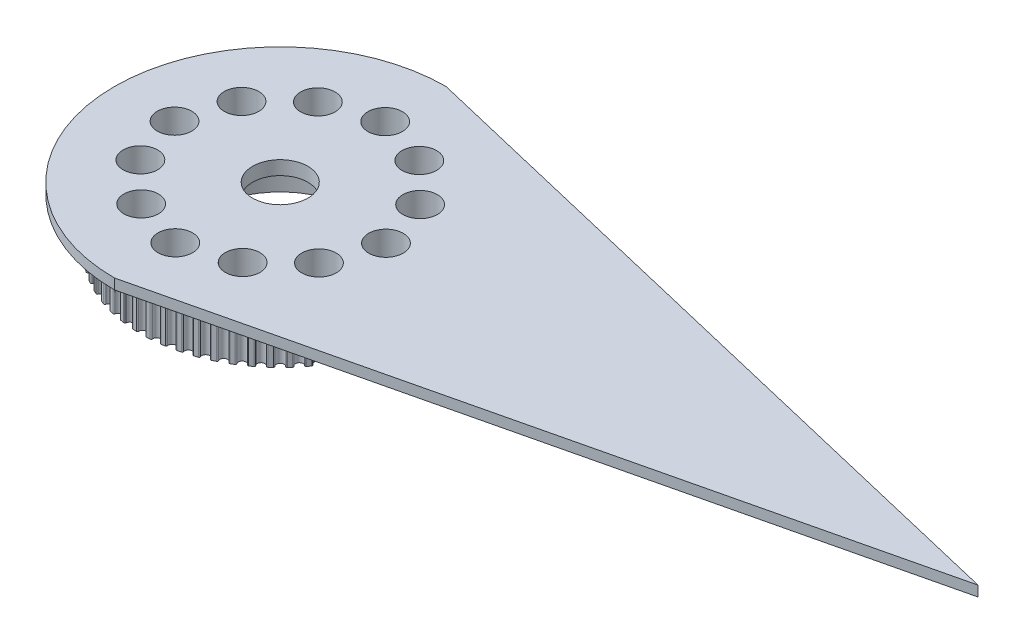
SolidWorks part; units mm, degrees
ref_plane "Front Plane" through (0, 0, 0) normal (0, 0, 1) x (1, 0, 0)
ref_plane "Top Plane" through (0, 0, 0) normal (0, 1, 0) x (1, 0, 0)
ref_plane "Right Plane" through (0, 0, 0) normal (1, 0, 0) x (0, 0, -1)
sketch "Sketch1" plane through (0, 0, 0) normal (0, 1, 0) x (1, 0, 0)
  line L2 (0, 24) -> (101, 0)
  line L3 (0, -24) -> (101, 0)
  arc A0 (0, 24) -> (0, -24) centre (0, 0) ccw
  point P5 (0, -12)
  dimension "D1" = 24
  dimension "D2" = 101
extrude "Boss-Extrude1" add sketch "Sketch1" along normal blind 1.5
sketch "Sketch2" plane through (0, 0, 0) normal (0, -1, 0) x (1, 0, 0)
  line L0 (0, 0) -> (0, 11) construction
  line L2 (0, 0) -> (1.0782, 10.947) construction
  circle A1 centre (0, 0) radius 11
  arc A3 (0, 19.37) -> (0.5544, 19.9506) centre (0, 19.925) ccw
  arc A4 (1.4038, 19.9089) -> (1.8986, 19.2767) centre (1.953, 19.8291) ccw
  arc A5 (0.7095, 20.1075) -> (0.5544, 19.9506) centre (0.7042, 19.9576) ccw
  arc A6 (1.4038, 19.9089) -> (1.2648, 20.0802) centre (1.2553, 19.9305) ccw
  arc A7 (1.2648, 20.0802) -> (0.7095, 20.1075) centre (0, 0) ccw
  arc A8 (1.8986, 19.2767) -> (2.5072, 19.8002) centre (1.953, 19.8291) ccw
  arc A9 (3.2269, 19.8595) -> (2.677, 19.9411) centre (0, 0) ccw
  arc A10 (3.3484, 19.6755) -> (3.7789, 18.9978) centre (3.8872, 19.5421) ccw
  arc A11 (3.3484, 19.6755) -> (3.2269, 19.8595) centre (3.2028, 19.7115) ccw
  arc A12 (2.677, 19.9411) -> (2.5072, 19.8002) centre (2.657, 19.7924) ccw
  arc A13 (3.7789, 18.9978) -> (4.4359, 19.4591) centre (3.8872, 19.5421) ccw
  arc A14 (5.1579, 19.4476) -> (4.6187, 19.5827) centre (0, 0) ccw
  arc A15 (5.2608, 19.2525) -> (5.6228, 18.5359) centre (5.7839, 19.067) ccw
  arc A16 (5.2608, 19.2525) -> (5.1579, 19.4476) centre (5.1195, 19.3026) ccw
  arc A17 (4.6187, 19.5827) -> (4.4359, 19.4591) centre (4.5842, 19.4367) ccw
  arc A18 (5.6228, 18.5359) -> (6.3219, 18.9306) centre (5.7839, 19.067) ccw
  arc A19 (7.0393, 18.8484) -> (6.5159, 19.0357) centre (0, 0) ccw
  arc A20 (7.1226, 18.6442) -> (7.4126, 17.8955) centre (7.625, 18.4083) ccw
  arc A21 (7.1226, 18.6442) -> (7.0393, 18.8484) centre (6.9868, 18.7079) ccw
  arc A22 (6.5159, 19.0357) -> (6.3219, 18.9306) centre (6.4673, 18.8938) ccw
  arc A23 (7.4126, 17.8955) -> (8.147, 18.2198) centre (7.625, 18.4083) ccw
  arc A24 (8.8528, 18.0677) -> (8.3503, 18.3054) centre (0, 0) ccw
  arc A25 (8.9157, 17.8562) -> (9.131, 17.0828) centre (9.3926, 17.5723) ccw
  arc A26 (8.9157, 17.8562) -> (8.8528, 18.0677) centre (8.7868, 17.933) ccw
  arc A27 (8.3503, 18.3054) -> (8.147, 18.2198) centre (8.2881, 18.1689) ccw
  arc A28 (9.131, 17.0828) -> (9.8936, 17.3336) centre (9.3926, 17.5723) ccw
  arc A29 (10.5812, 17.113) -> (10.1044, 17.3987) centre (0, 0) ccw
  arc A30 (10.623, 16.8964) -> (10.7614, 16.1056) centre (11.0697, 16.567) ccw
  arc A31 (10.623, 16.8964) -> (10.5812, 17.113) centre (10.5023, 16.9854) ccw
  arc A32 (10.1044, 17.3987) -> (9.8936, 17.3336) centre (10.029, 17.269) ccw
  arc A33 (10.7614, 16.1056) -> (11.545, 16.2803) centre (11.0697, 16.567) ccw
  arc A34 (12.2076, 15.9934) -> (11.7611, 16.3246) centre (0, 0) ccw
  arc A35 (12.228, 15.7738) -> (12.2882, 14.9732) centre (12.6403, 15.4022) ccw
  arc A36 (12.228, 15.7738) -> (12.2076, 15.9934) centre (12.1166, 15.8742) ccw
  arc A37 (11.7611, 16.3246) -> (11.545, 16.2803) centre (11.6734, 16.2029) ccw
  arc A38 (12.2882, 14.9732) -> (13.0851, 15.0703) centre (12.6403, 15.4022) ccw
  arc A39 (13.7164, 14.7199) -> (13.3045, 15.0932) centre (0, 0) ccw
  arc A40 (13.7152, 14.4993) -> (13.6967, 13.6967) centre (14.0891, 14.0891) ccw
  arc A41 (13.7152, 14.4993) -> (13.7164, 14.7199) centre (13.6142, 14.6101) ccw
  arc A42 (13.3045, 15.0932) -> (13.0851, 15.0703) centre (13.2053, 14.9806) ccw
  arc A43 (13.6967, 13.6967) -> (14.4993, 13.7152) centre (14.0891, 14.0891) ccw
  arc A44 (15.0932, 13.3045) -> (14.7199, 13.7164) centre (0, 0) ccw
  arc A45 (15.0703, 13.0851) -> (14.9732, 12.2882) centre (15.4022, 12.6403) ccw
  arc A46 (15.0703, 13.0851) -> (15.0932, 13.3045) centre (14.9806, 13.2053) ccw
  arc A47 (14.7199, 13.7164) -> (14.4993, 13.7152) centre (14.6101, 13.6142) ccw
  arc A48 (14.9732, 12.2882) -> (15.7738, 12.228) centre (15.4022, 12.6403) ccw
  arc A49 (16.3246, 11.7611) -> (15.9934, 12.2076) centre (0, 0) ccw
  arc A50 (16.2803, 11.545) -> (16.1056, 10.7614) centre (16.567, 11.0697) ccw
  arc A51 (16.2803, 11.545) -> (16.3246, 11.7611) centre (16.2029, 11.6734) ccw
  arc A52 (15.9934, 12.2076) -> (15.7738, 12.228) centre (15.8742, 12.1166) ccw
  arc A53 (16.1056, 10.7614) -> (16.8964, 10.623) centre (16.567, 11.0697) ccw
  arc A54 (17.3987, 10.1044) -> (17.113, 10.5812) centre (0, 0) ccw
  arc A55 (17.3336, 9.8936) -> (17.0828, 9.131) centre (17.5723, 9.3926) ccw
  arc A56 (17.3336, 9.8936) -> (17.3987, 10.1044) centre (17.269, 10.029) ccw
  arc A57 (17.113, 10.5812) -> (16.8964, 10.623) centre (16.9854, 10.5023) ccw
  arc A58 (17.0828, 9.131) -> (17.8562, 8.9157) centre (17.5723, 9.3926) ccw
  arc A59 (18.3054, 8.3503) -> (18.0677, 8.8528) centre (0, 0) ccw
  arc A60 (18.2198, 8.147) -> (17.8955, 7.4126) centre (18.4083, 7.625) ccw
  arc A61 (18.2198, 8.147) -> (18.3054, 8.3503) centre (18.1689, 8.2881) ccw
  arc A62 (18.0677, 8.8528) -> (17.8562, 8.9157) centre (17.933, 8.7868) ccw
  arc A63 (17.8955, 7.4126) -> (18.6442, 7.1226) centre (18.4083, 7.625) ccw
  arc A64 (19.0357, 6.5159) -> (18.8484, 7.0393) centre (0, 0) ccw
  arc A65 (18.9306, 6.3219) -> (18.5359, 5.6228) centre (19.067, 5.7839) ccw
  arc A66 (18.9306, 6.3219) -> (19.0357, 6.5159) centre (18.8938, 6.4673) ccw
  arc A67 (18.8484, 7.0393) -> (18.6442, 7.1226) centre (18.7079, 6.9868) ccw
  arc A68 (18.5359, 5.6228) -> (19.2525, 5.2608) centre (19.067, 5.7839) ccw
  arc A69 (19.5827, 4.6187) -> (19.4476, 5.1579) centre (0, 0) ccw
  arc A70 (19.4591, 4.4359) -> (18.9978, 3.7789) centre (19.5421, 3.8872) ccw
  arc A71 (19.4591, 4.4359) -> (19.5827, 4.6187) centre (19.4367, 4.5842) ccw
  arc A72 (19.4476, 5.1579) -> (19.2525, 5.2608) centre (19.3026, 5.1195) ccw
  arc A73 (18.9978, 3.7789) -> (19.6755, 3.3484) centre (19.5421, 3.8872) ccw
  arc A74 (19.9411, 2.677) -> (19.8595, 3.2269) centre (0, 0) ccw
  arc A75 (19.8002, 2.5072) -> (19.2767, 1.8986) centre (19.8291, 1.953) ccw
  arc A76 (19.8002, 2.5072) -> (19.9411, 2.677) centre (19.7924, 2.657) ccw
  arc A77 (19.8595, 3.2269) -> (19.6755, 3.3484) centre (19.7115, 3.2028) ccw
  arc A78 (19.2767, 1.8986) -> (19.9089, 1.4038) centre (19.8291, 1.953) ccw
  arc A79 (20.1075, 0.7095) -> (20.0802, 1.2648) centre (0, 0) ccw
  arc A80 (19.9506, 0.5544) -> (19.37, 0) centre (19.925, 0) ccw
  arc A81 (19.9506, 0.5544) -> (20.1075, 0.7095) centre (19.9576, 0.7042) ccw
  arc A82 (20.0802, 1.2648) -> (19.9089, 1.4038) centre (19.9305, 1.2553) ccw
  arc A83 (19.37, 0) -> (19.9506, -0.5544) centre (19.925, 0) ccw
  arc A84 (20.0802, -1.2648) -> (20.1075, -0.7095) centre (0, 0) ccw
  arc A85 (19.9089, -1.4038) -> (19.2767, -1.8986) centre (19.8291, -1.953) ccw
  arc A86 (19.9089, -1.4038) -> (20.0802, -1.2648) centre (19.9305, -1.2553) ccw
  arc A87 (20.1075, -0.7095) -> (19.9506, -0.5544) centre (19.9576, -0.7042) ccw
  arc A88 (19.2767, -1.8986) -> (19.8002, -2.5072) centre (19.8291, -1.953) ccw
  arc A89 (19.8595, -3.2269) -> (19.9411, -2.677) centre (0, 0) ccw
  arc A90 (19.6755, -3.3484) -> (18.9978, -3.7789) centre (19.5421, -3.8872) ccw
  arc A91 (19.6755, -3.3484) -> (19.8595, -3.2269) centre (19.7115, -3.2028) ccw
  arc A92 (19.9411, -2.677) -> (19.8002, -2.5072) centre (19.7924, -2.657) ccw
  arc A93 (18.9978, -3.7789) -> (19.4591, -4.4359) centre (19.5421, -3.8872) ccw
  arc A94 (19.4476, -5.1579) -> (19.5827, -4.6187) centre (0, 0) ccw
  arc A95 (19.2525, -5.2608) -> (18.5359, -5.6228) centre (19.067, -5.7839) ccw
  arc A96 (19.2525, -5.2608) -> (19.4476, -5.1579) centre (19.3026, -5.1195) ccw
  arc A97 (19.5827, -4.6187) -> (19.4591, -4.4359) centre (19.4367, -4.5842) ccw
  arc A98 (18.5359, -5.6228) -> (18.9306, -6.3219) centre (19.067, -5.7839) ccw
  arc A99 (18.8484, -7.0393) -> (19.0357, -6.5159) centre (0, 0) ccw
  arc A100 (18.6442, -7.1226) -> (17.8955, -7.4126) centre (18.4083, -7.625) ccw
  arc A101 (18.6442, -7.1226) -> (18.8484, -7.0393) centre (18.7079, -6.9868) ccw
  arc A102 (19.0357, -6.5159) -> (18.9306, -6.3219) centre (18.8938, -6.4673) ccw
  arc A103 (17.8955, -7.4126) -> (18.2198, -8.147) centre (18.4083, -7.625) ccw
  arc A104 (18.0677, -8.8528) -> (18.3054, -8.3503) centre (0, 0) ccw
  arc A105 (17.8562, -8.9157) -> (17.0828, -9.131) centre (17.5723, -9.3926) ccw
  arc A106 (17.8562, -8.9157) -> (18.0677, -8.8528) centre (17.933, -8.7868) ccw
  arc A107 (18.3054, -8.3503) -> (18.2198, -8.147) centre (18.1689, -8.2881) ccw
  arc A108 (17.0828, -9.131) -> (17.3336, -9.8936) centre (17.5723, -9.3926) ccw
  arc A109 (17.113, -10.5812) -> (17.3987, -10.1044) centre (0, 0) ccw
  arc A110 (16.8964, -10.623) -> (16.1056, -10.7614) centre (16.567, -11.0697) ccw
  arc A111 (16.8964, -10.623) -> (17.113, -10.5812) centre (16.9854, -10.5023) ccw
  arc A112 (17.3987, -10.1044) -> (17.3336, -9.8936) centre (17.269, -10.029) ccw
  arc A113 (16.1056, -10.7614) -> (16.2803, -11.545) centre (16.567, -11.0697) ccw
  arc A114 (15.9934, -12.2076) -> (16.3246, -11.7611) centre (0, 0) ccw
  arc A115 (15.7738, -12.228) -> (14.9732, -12.2882) centre (15.4022, -12.6403) ccw
  arc A116 (15.7738, -12.228) -> (15.9934, -12.2076) centre (15.8742, -12.1166) ccw
  arc A117 (16.3246, -11.7611) -> (16.2803, -11.545) centre (16.2029, -11.6734) ccw
  arc A118 (14.9732, -12.2882) -> (15.0703, -13.0851) centre (15.4022, -12.6403) ccw
  arc A119 (14.7199, -13.7164) -> (15.0932, -13.3045) centre (0, 0) ccw
  arc A120 (14.4993, -13.7152) -> (13.6967, -13.6967) centre (14.0891, -14.0891) ccw
  arc A121 (14.4993, -13.7152) -> (14.7199, -13.7164) centre (14.6101, -13.6142) ccw
  arc A122 (15.0932, -13.3045) -> (15.0703, -13.0851) centre (14.9806, -13.2053) ccw
  arc A123 (13.6967, -13.6967) -> (13.7152, -14.4993) centre (14.0891, -14.0891) ccw
  arc A124 (13.3045, -15.0932) -> (13.7164, -14.7199) centre (0, 0) ccw
  arc A125 (13.0851, -15.0703) -> (12.2882, -14.9732) centre (12.6403, -15.4022) ccw
  arc A126 (13.0851, -15.0703) -> (13.3045, -15.0932) centre (13.2053, -14.9806) ccw
  arc A127 (13.7164, -14.7199) -> (13.7152, -14.4993) centre (13.6142, -14.6101) ccw
  arc A128 (12.2882, -14.9732) -> (12.228, -15.7738) centre (12.6403, -15.4022) ccw
  arc A129 (11.7611, -16.3246) -> (12.2076, -15.9934) centre (0, 0) ccw
  arc A130 (11.545, -16.2803) -> (10.7614, -16.1056) centre (11.0697, -16.567) ccw
  arc A131 (11.545, -16.2803) -> (11.7611, -16.3246) centre (11.6734, -16.2029) ccw
  arc A132 (12.2076, -15.9934) -> (12.228, -15.7738) centre (12.1166, -15.8742) ccw
  arc A133 (10.7614, -16.1056) -> (10.623, -16.8964) centre (11.0697, -16.567) ccw
  arc A134 (10.1044, -17.3987) -> (10.5812, -17.113) centre (0, 0) ccw
  arc A135 (9.8936, -17.3336) -> (9.131, -17.0828) centre (9.3926, -17.5723) ccw
  arc A136 (9.8936, -17.3336) -> (10.1044, -17.3987) centre (10.029, -17.269) ccw
  arc A137 (10.5812, -17.113) -> (10.623, -16.8964) centre (10.5023, -16.9854) ccw
  arc A138 (9.131, -17.0828) -> (8.9157, -17.8562) centre (9.3926, -17.5723) ccw
  arc A139 (8.3503, -18.3054) -> (8.8528, -18.0677) centre (0, 0) ccw
  arc A140 (8.147, -18.2198) -> (7.4126, -17.8955) centre (7.625, -18.4083) ccw
  arc A141 (8.147, -18.2198) -> (8.3503, -18.3054) centre (8.2881, -18.1689) ccw
  arc A142 (8.8528, -18.0677) -> (8.9157, -17.8562) centre (8.7868, -17.933) ccw
  arc A143 (7.4126, -17.8955) -> (7.1226, -18.6442) centre (7.625, -18.4083) ccw
  arc A144 (6.5159, -19.0357) -> (7.0393, -18.8484) centre (0, 0) ccw
  arc A145 (6.3219, -18.9306) -> (5.6228, -18.5359) centre (5.7839, -19.067) ccw
  arc A146 (6.3219, -18.9306) -> (6.5159, -19.0357) centre (6.4673, -18.8938) ccw
  arc A147 (7.0393, -18.8484) -> (7.1226, -18.6442) centre (6.9868, -18.7079) ccw
  arc A148 (5.6228, -18.5359) -> (5.2608, -19.2525) centre (5.7839, -19.067) ccw
  arc A149 (4.6187, -19.5827) -> (5.1579, -19.4476) centre (0, 0) ccw
  arc A150 (4.4359, -19.4591) -> (3.7789, -18.9978) centre (3.8872, -19.5421) ccw
  arc A151 (4.4359, -19.4591) -> (4.6187, -19.5827) centre (4.5842, -19.4367) ccw
  arc A152 (5.1579, -19.4476) -> (5.2608, -19.2525) centre (5.1195, -19.3026) ccw
  arc A153 (3.7789, -18.9978) -> (3.3484, -19.6755) centre (3.8872, -19.5421) ccw
  arc A154 (2.677, -19.9411) -> (3.2269, -19.8595) centre (0, 0) ccw
  arc A155 (2.5072, -19.8002) -> (1.8986, -19.2767) centre (1.953, -19.8291) ccw
  arc A156 (2.5072, -19.8002) -> (2.677, -19.9411) centre (2.657, -19.7924) ccw
  arc A157 (3.2269, -19.8595) -> (3.3484, -19.6755) centre (3.2028, -19.7115) ccw
  arc A158 (1.8986, -19.2767) -> (1.4038, -19.9089) centre (1.953, -19.8291) ccw
  arc A159 (0.7095, -20.1075) -> (1.2648, -20.0802) centre (0, 0) ccw
  arc A160 (0.5544, -19.9506) -> (0, -19.37) centre (0, -19.925) ccw
  arc A161 (0.5544, -19.9506) -> (0.7095, -20.1075) centre (0.7042, -19.9576) ccw
  arc A162 (1.2648, -20.0802) -> (1.4038, -19.9089) centre (1.2553, -19.9305) ccw
  arc A163 (0, -19.37) -> (-0.5544, -19.9506) centre (0, -19.925) ccw
  arc A164 (-1.2648, -20.0802) -> (-0.7095, -20.1075) centre (0, 0) ccw
  arc A165 (-1.4038, -19.9089) -> (-1.8986, -19.2767) centre (-1.953, -19.8291) ccw
  arc A166 (-1.4038, -19.9089) -> (-1.2648, -20.0802) centre (-1.2553, -19.9305) ccw
  arc A167 (-0.7095, -20.1075) -> (-0.5544, -19.9506) centre (-0.7042, -19.9576) ccw
  arc A168 (-1.8986, -19.2767) -> (-2.5072, -19.8002) centre (-1.953, -19.8291) ccw
  arc A169 (-3.2269, -19.8595) -> (-2.677, -19.9411) centre (0, 0) ccw
  arc A170 (-3.3484, -19.6755) -> (-3.7789, -18.9978) centre (-3.8872, -19.5421) ccw
  arc A171 (-3.3484, -19.6755) -> (-3.2269, -19.8595) centre (-3.2028, -19.7115) ccw
  arc A172 (-2.677, -19.9411) -> (-2.5072, -19.8002) centre (-2.657, -19.7924) ccw
  arc A173 (-3.7789, -18.9978) -> (-4.4359, -19.4591) centre (-3.8872, -19.5421) ccw
  arc A174 (-5.1579, -19.4476) -> (-4.6187, -19.5827) centre (0, 0) ccw
  arc A175 (-5.2608, -19.2525) -> (-5.6228, -18.5359) centre (-5.7839, -19.067) ccw
  arc A176 (-5.2608, -19.2525) -> (-5.1579, -19.4476) centre (-5.1195, -19.3026) ccw
  arc A177 (-4.6187, -19.5827) -> (-4.4359, -19.4591) centre (-4.5842, -19.4367) ccw
  arc A178 (-5.6228, -18.5359) -> (-6.3219, -18.9306) centre (-5.7839, -19.067) ccw
  arc A179 (-7.0393, -18.8484) -> (-6.5159, -19.0357) centre (0, 0) ccw
  arc A180 (-7.1226, -18.6442) -> (-7.4126, -17.8955) centre (-7.625, -18.4083) ccw
  arc A181 (-7.1226, -18.6442) -> (-7.0393, -18.8484) centre (-6.9868, -18.7079) ccw
  arc A182 (-6.5159, -19.0357) -> (-6.3219, -18.9306) centre (-6.4673, -18.8938) ccw
  arc A183 (-7.4126, -17.8955) -> (-8.147, -18.2198) centre (-7.625, -18.4083) ccw
  arc A184 (-8.8528, -18.0677) -> (-8.3503, -18.3054) centre (0, 0) ccw
  arc A185 (-8.9157, -17.8562) -> (-9.131, -17.0828) centre (-9.3926, -17.5723) ccw
  arc A186 (-8.9157, -17.8562) -> (-8.8528, -18.0677) centre (-8.7868, -17.933) ccw
  arc A187 (-8.3503, -18.3054) -> (-8.147, -18.2198) centre (-8.2881, -18.1689) ccw
  arc A188 (-9.131, -17.0828) -> (-9.8936, -17.3336) centre (-9.3926, -17.5723) ccw
  arc A189 (-10.5812, -17.113) -> (-10.1044, -17.3987) centre (0, 0) ccw
  arc A190 (-10.623, -16.8964) -> (-10.7614, -16.1056) centre (-11.0697, -16.567) ccw
  arc A191 (-10.623, -16.8964) -> (-10.5812, -17.113) centre (-10.5023, -16.9854) ccw
  arc A192 (-10.1044, -17.3987) -> (-9.8936, -17.3336) centre (-10.029, -17.269) ccw
  arc A193 (-10.7614, -16.1056) -> (-11.545, -16.2803) centre (-11.0697, -16.567) ccw
  arc A194 (-12.2076, -15.9934) -> (-11.7611, -16.3246) centre (0, 0) ccw
  arc A195 (-12.228, -15.7738) -> (-12.2882, -14.9732) centre (-12.6403, -15.4022) ccw
  arc A196 (-12.228, -15.7738) -> (-12.2076, -15.9934) centre (-12.1166, -15.8742) ccw
  arc A197 (-11.7611, -16.3246) -> (-11.545, -16.2803) centre (-11.6734, -16.2029) ccw
  arc A198 (-12.2882, -14.9732) -> (-13.0851, -15.0703) centre (-12.6403, -15.4022) ccw
  arc A199 (-13.7164, -14.7199) -> (-13.3045, -15.0932) centre (0, 0) ccw
  arc A200 (-13.7152, -14.4993) -> (-13.6967, -13.6967) centre (-14.0891, -14.0891) ccw
  arc A201 (-13.7152, -14.4993) -> (-13.7164, -14.7199) centre (-13.6142, -14.6101) ccw
  arc A202 (-13.3045, -15.0932) -> (-13.0851, -15.0703) centre (-13.2053, -14.9806) ccw
  arc A203 (-13.6967, -13.6967) -> (-14.4993, -13.7152) centre (-14.0891, -14.0891) ccw
  arc A204 (-15.0932, -13.3045) -> (-14.7199, -13.7164) centre (0, 0) ccw
  arc A205 (-15.0703, -13.0851) -> (-14.9732, -12.2882) centre (-15.4022, -12.6403) ccw
  arc A206 (-15.0703, -13.0851) -> (-15.0932, -13.3045) centre (-14.9806, -13.2053) ccw
  arc A207 (-14.7199, -13.7164) -> (-14.4993, -13.7152) centre (-14.6101, -13.6142) ccw
  arc A208 (-14.9732, -12.2882) -> (-15.7738, -12.228) centre (-15.4022, -12.6403) ccw
  arc A209 (-16.3246, -11.7611) -> (-15.9934, -12.2076) centre (0, 0) ccw
  arc A210 (-16.2803, -11.545) -> (-16.1056, -10.7614) centre (-16.567, -11.0697) ccw
  arc A211 (-16.2803, -11.545) -> (-16.3246, -11.7611) centre (-16.2029, -11.6734) ccw
  arc A212 (-15.9934, -12.2076) -> (-15.7738, -12.228) centre (-15.8742, -12.1166) ccw
  arc A213 (-16.1056, -10.7614) -> (-16.8964, -10.623) centre (-16.567, -11.0697) ccw
  arc A214 (-17.3987, -10.1044) -> (-17.113, -10.5812) centre (0, 0) ccw
  arc A215 (-17.3336, -9.8936) -> (-17.0828, -9.131) centre (-17.5723, -9.3926) ccw
  arc A216 (-17.3336, -9.8936) -> (-17.3987, -10.1044) centre (-17.269, -10.029) ccw
  arc A217 (-17.113, -10.5812) -> (-16.8964, -10.623) centre (-16.9854, -10.5023) ccw
  arc A218 (-17.0828, -9.131) -> (-17.8562, -8.9157) centre (-17.5723, -9.3926) ccw
  arc A219 (-18.3054, -8.3503) -> (-18.0677, -8.8528) centre (0, 0) ccw
  arc A220 (-18.2198, -8.147) -> (-17.8955, -7.4126) centre (-18.4083, -7.625) ccw
  arc A221 (-18.2198, -8.147) -> (-18.3054, -8.3503) centre (-18.1689, -8.2881) ccw
  arc A222 (-18.0677, -8.8528) -> (-17.8562, -8.9157) centre (-17.933, -8.7868) ccw
  arc A223 (-17.8955, -7.4126) -> (-18.6442, -7.1226) centre (-18.4083, -7.625) ccw
  arc A224 (-19.0357, -6.5159) -> (-18.8484, -7.0393) centre (0, 0) ccw
  arc A225 (-18.9306, -6.3219) -> (-18.5359, -5.6228) centre (-19.067, -5.7839) ccw
  arc A226 (-18.9306, -6.3219) -> (-19.0357, -6.5159) centre (-18.8938, -6.4673) ccw
  arc A227 (-18.8484, -7.0393) -> (-18.6442, -7.1226) centre (-18.7079, -6.9868) ccw
  arc A228 (-18.5359, -5.6228) -> (-19.2525, -5.2608) centre (-19.067, -5.7839) ccw
  arc A229 (-19.5827, -4.6187) -> (-19.4476, -5.1579) centre (0, 0) ccw
  arc A230 (-19.4591, -4.4359) -> (-18.9978, -3.7789) centre (-19.5421, -3.8872) ccw
  arc A231 (-19.4591, -4.4359) -> (-19.5827, -4.6187) centre (-19.4367, -4.5842) ccw
  arc A232 (-19.4476, -5.1579) -> (-19.2525, -5.2608) centre (-19.3026, -5.1195) ccw
  arc A233 (-18.9978, -3.7789) -> (-19.6755, -3.3484) centre (-19.5421, -3.8872) ccw
  arc A234 (-19.9411, -2.677) -> (-19.8595, -3.2269) centre (0, 0) ccw
  arc A235 (-19.8002, -2.5072) -> (-19.2767, -1.8986) centre (-19.8291, -1.953) ccw
  arc A236 (-19.8002, -2.5072) -> (-19.9411, -2.677) centre (-19.7924, -2.657) ccw
  arc A237 (-19.8595, -3.2269) -> (-19.6755, -3.3484) centre (-19.7115, -3.2028) ccw
  arc A238 (-19.2767, -1.8986) -> (-19.9089, -1.4038) centre (-19.8291, -1.953) ccw
  arc A239 (-20.1075, -0.7095) -> (-20.0802, -1.2648) centre (0, 0) ccw
  arc A240 (-19.9506, -0.5544) -> (-19.37, 0) centre (-19.925, 0) ccw
  arc A241 (-19.9506, -0.5544) -> (-20.1075, -0.7095) centre (-19.9576, -0.7042) ccw
  arc A242 (-20.0802, -1.2648) -> (-19.9089, -1.4038) centre (-19.9305, -1.2553) ccw
  arc A243 (-19.37, 0) -> (-19.9506, 0.5544) centre (-19.925, 0) ccw
  arc A244 (-20.0802, 1.2648) -> (-20.1075, 0.7095) centre (0, 0) ccw
  arc A245 (-19.9089, 1.4038) -> (-19.2767, 1.8986) centre (-19.8291, 1.953) ccw
  arc A246 (-19.9089, 1.4038) -> (-20.0802, 1.2648) centre (-19.9305, 1.2553) ccw
  arc A247 (-20.1075, 0.7095) -> (-19.9506, 0.5544) centre (-19.9576, 0.7042) ccw
  arc A248 (-19.2767, 1.8986) -> (-19.8002, 2.5072) centre (-19.8291, 1.953) ccw
  arc A249 (-19.8595, 3.2269) -> (-19.9411, 2.677) centre (0, 0) ccw
  arc A250 (-19.6755, 3.3484) -> (-18.9978, 3.7789) centre (-19.5421, 3.8872) ccw
  arc A251 (-19.6755, 3.3484) -> (-19.8595, 3.2269) centre (-19.7115, 3.2028) ccw
  arc A252 (-19.9411, 2.677) -> (-19.8002, 2.5072) centre (-19.7924, 2.657) ccw
  arc A253 (-18.9978, 3.7789) -> (-19.4591, 4.4359) centre (-19.5421, 3.8872) ccw
  arc A254 (-19.4476, 5.1579) -> (-19.5827, 4.6187) centre (0, 0) ccw
  arc A255 (-19.2525, 5.2608) -> (-18.5359, 5.6228) centre (-19.067, 5.7839) ccw
  arc A256 (-19.2525, 5.2608) -> (-19.4476, 5.1579) centre (-19.3026, 5.1195) ccw
  arc A257 (-19.5827, 4.6187) -> (-19.4591, 4.4359) centre (-19.4367, 4.5842) ccw
  arc A258 (-18.5359, 5.6228) -> (-18.9306, 6.3219) centre (-19.067, 5.7839) ccw
  arc A259 (-18.8484, 7.0393) -> (-19.0357, 6.5159) centre (0, 0) ccw
  arc A260 (-18.6442, 7.1226) -> (-17.8955, 7.4126) centre (-18.4083, 7.625) ccw
  arc A261 (-18.6442, 7.1226) -> (-18.8484, 7.0393) centre (-18.7079, 6.9868) ccw
  arc A262 (-19.0357, 6.5159) -> (-18.9306, 6.3219) centre (-18.8938, 6.4673) ccw
  arc A263 (-17.8955, 7.4126) -> (-18.2198, 8.147) centre (-18.4083, 7.625) ccw
  arc A264 (-18.0677, 8.8528) -> (-18.3054, 8.3503) centre (0, 0) ccw
  arc A265 (-17.8562, 8.9157) -> (-17.0828, 9.131) centre (-17.5723, 9.3926) ccw
  arc A266 (-17.8562, 8.9157) -> (-18.0677, 8.8528) centre (-17.933, 8.7868) ccw
  arc A267 (-18.3054, 8.3503) -> (-18.2198, 8.147) centre (-18.1689, 8.2881) ccw
  arc A268 (-17.0828, 9.131) -> (-17.3336, 9.8936) centre (-17.5723, 9.3926) ccw
  arc A269 (-17.113, 10.5812) -> (-17.3987, 10.1044) centre (0, 0) ccw
  arc A270 (-16.8964, 10.623) -> (-16.1056, 10.7614) centre (-16.567, 11.0697) ccw
  arc A271 (-16.8964, 10.623) -> (-17.113, 10.5812) centre (-16.9854, 10.5023) ccw
  arc A272 (-17.3987, 10.1044) -> (-17.3336, 9.8936) centre (-17.269, 10.029) ccw
  arc A273 (-16.1056, 10.7614) -> (-16.2803, 11.545) centre (-16.567, 11.0697) ccw
  arc A274 (-15.9934, 12.2076) -> (-16.3246, 11.7611) centre (0, 0) ccw
  arc A275 (-15.7738, 12.228) -> (-14.9732, 12.2882) centre (-15.4022, 12.6403) ccw
  arc A276 (-15.7738, 12.228) -> (-15.9934, 12.2076) centre (-15.8742, 12.1166) ccw
  arc A277 (-16.3246, 11.7611) -> (-16.2803, 11.545) centre (-16.2029, 11.6734) ccw
  arc A278 (-14.9732, 12.2882) -> (-15.0703, 13.0851) centre (-15.4022, 12.6403) ccw
  arc A279 (-14.7199, 13.7164) -> (-15.0932, 13.3045) centre (0, 0) ccw
  arc A280 (-14.4993, 13.7152) -> (-13.6967, 13.6967) centre (-14.0891, 14.0891) ccw
  arc A281 (-14.4993, 13.7152) -> (-14.7199, 13.7164) centre (-14.6101, 13.6142) ccw
  arc A282 (-15.0932, 13.3045) -> (-15.0703, 13.0851) centre (-14.9806, 13.2053) ccw
  arc A283 (-13.6967, 13.6967) -> (-13.7152, 14.4993) centre (-14.0891, 14.0891) ccw
  arc A284 (-13.3045, 15.0932) -> (-13.7164, 14.7199) centre (0, 0) ccw
  arc A285 (-13.0851, 15.0703) -> (-12.2882, 14.9732) centre (-12.6403, 15.4022) ccw
  arc A286 (-13.0851, 15.0703) -> (-13.3045, 15.0932) centre (-13.2053, 14.9806) ccw
  arc A287 (-13.7164, 14.7199) -> (-13.7152, 14.4993) centre (-13.6142, 14.6101) ccw
  arc A288 (-12.2882, 14.9732) -> (-12.228, 15.7738) centre (-12.6403, 15.4022) ccw
  arc A289 (-11.7611, 16.3246) -> (-12.2076, 15.9934) centre (0, 0) ccw
  arc A290 (-11.545, 16.2803) -> (-10.7614, 16.1056) centre (-11.0697, 16.567) ccw
  arc A291 (-11.545, 16.2803) -> (-11.7611, 16.3246) centre (-11.6734, 16.2029) ccw
  arc A292 (-12.2076, 15.9934) -> (-12.228, 15.7738) centre (-12.1166, 15.8742) ccw
  arc A293 (-10.7614, 16.1056) -> (-10.623, 16.8964) centre (-11.0697, 16.567) ccw
  arc A294 (-10.1044, 17.3987) -> (-10.5812, 17.113) centre (0, 0) ccw
  arc A295 (-9.8936, 17.3336) -> (-9.131, 17.0828) centre (-9.3926, 17.5723) ccw
  arc A296 (-9.8936, 17.3336) -> (-10.1044, 17.3987) centre (-10.029, 17.269) ccw
  arc A297 (-10.5812, 17.113) -> (-10.623, 16.8964) centre (-10.5023, 16.9854) ccw
  arc A298 (-9.131, 17.0828) -> (-8.9157, 17.8562) centre (-9.3926, 17.5723) ccw
  arc A299 (-8.3503, 18.3054) -> (-8.8528, 18.0677) centre (0, 0) ccw
  arc A300 (-8.147, 18.2198) -> (-7.4126, 17.8955) centre (-7.625, 18.4083) ccw
  arc A301 (-8.147, 18.2198) -> (-8.3503, 18.3054) centre (-8.2881, 18.1689) ccw
  arc A302 (-8.8528, 18.0677) -> (-8.9157, 17.8562) centre (-8.7868, 17.933) ccw
  arc A303 (-7.4126, 17.8955) -> (-7.1226, 18.6442) centre (-7.625, 18.4083) ccw
  arc A304 (-6.5159, 19.0357) -> (-7.0393, 18.8484) centre (0, 0) ccw
  arc A305 (-6.3219, 18.9306) -> (-5.6228, 18.5359) centre (-5.7839, 19.067) ccw
  arc A306 (-6.3219, 18.9306) -> (-6.5159, 19.0357) centre (-6.4673, 18.8938) ccw
  arc A307 (-7.0393, 18.8484) -> (-7.1226, 18.6442) centre (-6.9868, 18.7079) ccw
  arc A308 (-5.6228, 18.5359) -> (-5.2608, 19.2525) centre (-5.7839, 19.067) ccw
  arc A309 (-4.6187, 19.5827) -> (-5.1579, 19.4476) centre (0, 0) ccw
  arc A310 (-4.4359, 19.4591) -> (-3.7789, 18.9978) centre (-3.8872, 19.5421) ccw
  arc A311 (-4.4359, 19.4591) -> (-4.6187, 19.5827) centre (-4.5842, 19.4367) ccw
  arc A312 (-5.1579, 19.4476) -> (-5.2608, 19.2525) centre (-5.1195, 19.3026) ccw
  arc A313 (-3.7789, 18.9978) -> (-3.3484, 19.6755) centre (-3.8872, 19.5421) ccw
  arc A314 (-2.677, 19.9411) -> (-3.2269, 19.8595) centre (0, 0) ccw
  arc A315 (-2.5072, 19.8002) -> (-1.8986, 19.2767) centre (-1.953, 19.8291) ccw
  arc A316 (-2.5072, 19.8002) -> (-2.677, 19.9411) centre (-2.657, 19.7924) ccw
  arc A317 (-3.2269, 19.8595) -> (-3.3484, 19.6755) centre (-3.2028, 19.7115) ccw
  arc A318 (-1.8986, 19.2767) -> (-1.4038, 19.9089) centre (-1.953, 19.8291) ccw
  arc A319 (-0.7095, 20.1075) -> (-1.2648, 20.0802) centre (0, 0) ccw
  arc A320 (-0.5544, 19.9506) -> (0, 19.37) centre (0, 19.925) ccw
  arc A321 (-0.5544, 19.9506) -> (-0.7095, 20.1075) centre (-0.7042, 19.9576) ccw
  arc A322 (-1.2648, 20.0802) -> (-1.4038, 19.9089) centre (-1.2553, 19.9305) ccw
  point P650 (0, 0)
  dimension "D2" = 64
  dimension "D4" = 1.11
  dimension "D5" = 1.11
  dimension "D6" = 0.3
  dimension "D7" = 0.3
extrude "Boss-Extrude3" add sketch "Sketch2" along normal blind 7.5
sketch "Sketch3" plane through (0, 0, 0) normal (0, -1, 0) x (1, 0, 0)
  circle A0 centre (0, 0) radius 6
  circle A1 centre (0, 0) radius 4
extrude "Boss-Extrude4" add sketch "Sketch3" along normal blind 0.5
sketch "Sketch4" plane through (0, 0, 0) normal (0, -1, 0) x (-1, 0, 0)
  circle A0 centre (0, 0) radius 4
extrude "Cut-Extrude1" cut sketch "Sketch4" against normal through all
sketch "Sketch5" plane through (0, -7.5, 0) normal (0, -1, 0) x (1, 0, 0)
  line L1 (-25.5726, 0) -> (27.0963, 0) construction
  line L3 (0, -21.348) -> (0, 25.1162) construction
  circle A0 centre (-15.3004, 0) radius 2.5
  circle A1 centre (-12.9246, 7.3208) radius 2.5
  circle A2 centre (-7.343, 12.7878) radius 2.5
  circle A3 centre (7.343, 12.7878) radius 2.5
  circle A4 centre (12.9246, 7.3208) radius 2.5
  circle A5 centre (15.3004, 0) radius 2.5
  circle A6 centre (0, 15.1922) radius 2.5
  circle A7 centre (12.9246, -7.3208) radius 2.5
  circle A8 centre (7.343, -12.7878) radius 2.5
  circle A9 centre (0, -15.1922) radius 2.5
  circle A10 centre (-7.343, -12.7878) radius 2.5
  circle A11 centre (-12.9246, -7.3208) radius 2.5
  point P11 (-12.8101, 8.0936)
  point P12 (-7.343, 12.7878)
  point P13 (-12.9246, 7.3208)
  point P22 (0, 15.1922)
extrude "Cut-Extrude2" cut sketch "Sketch5" against normal through all
